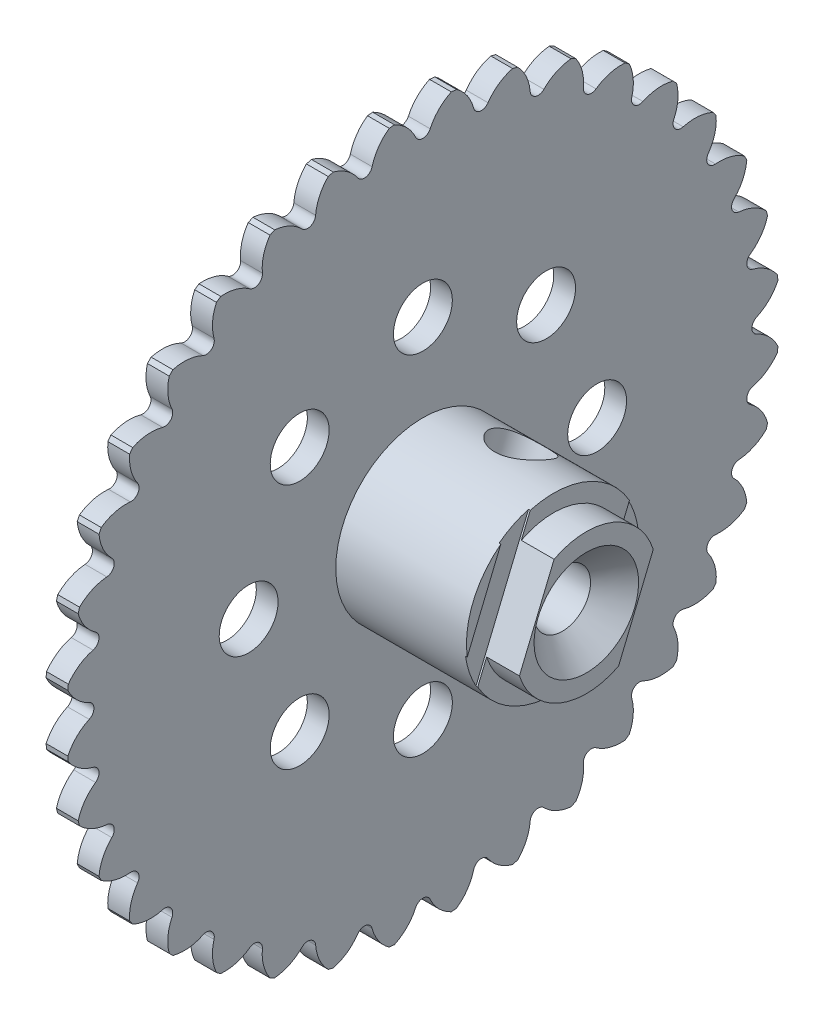
SolidWorks part; units mm, degrees
ref_plane "Front Plane" through (0, 0, 0) normal (0, 0, 1) x (1, 0, 0)
ref_plane "Top Plane" through (0, 0, 0) normal (0, 1, 0) x (1, 0, 0)
ref_plane "Right Plane" through (0, 0, 0) normal (1, 0, 0) x (0, 0, -1)
sketch "Sketch1" plane through (0, 0, 0) normal (1, 0, 0) x (0, 0, -1)
  circle A0 centre (0, 0) radius 25.9588
  dimension "D1" = 51.9176
extrude "Boss-Extrude1" add sketch "Sketch1" along normal blind 1.5875
sketch "Sketch2" plane through (1.5875, 0, 0) normal (1, 0, 0) x (0, 0, -1)
  circle A0 centre (0, 0) radius 12.7 construction
  circle A1 centre (0, 12.7) radius 2.1463
  dimension "D1" = 25.4
  dimension "D2" = 4.2926
extrude "Cut-Extrude1" cut sketch "Sketch2" against normal blind 1.5875
pattern_circular "CirPattern1" count 8 over 360 about axis through (1.5875, 0, 0) along (1, 0, 0) of "Cut-Extrude1"
sketch "Sketch4" plane through (1.5875, 0, 0) normal (1, 0, 0) x (0, 0, -1)
  line L0 (0, 23.9776) -> (0, 25.9588) construction
  line L1 (0, 0.8731) -> (0, -0.8731) construction
  line L2 (0, 0) -> (-2.0726, 25.8759) construction
  line L3 (0, 0) -> (2.4522, 25.8427) construction
  arc A0 (-2.0726, 25.8759) -> (-0.5315, 24.3192) centre (-3.4198, 23.0009) cw
  circle A1 centre (0, 0) radius 25.9588 construction
  arc A2 (-0.5315, 24.3192) -> (0.5315, 24.3192) centre (0, 24.5618) ccw
  arc A3 (0.5315, 24.3192) -> (2.0726, 25.8759) centre (3.4198, 23.0009) cw
  arc A4 (-2.0726, 25.8759) -> (2.4522, 25.8427) centre (0, 0) cw
  circle M13 centre (0, 0) radius 25.9588
  dimension "D1" = 0.5842
  dimension "D2" = 3.175
  dimension "D3" = 1.9812
  dimension "D4" = 10
  dimension "D5" = 0.381
extrude "Cut-Extrude2" cut sketch "Sketch4" against normal blind 1.5875 contours A2 A3 A0 M13 region at (1.5875, 25.2328, 0)
pattern_circular "CirPattern2" count 36 over 360 about axis through (1.5875, 0, 0) along (1, 0, 0) of "Cut-Extrude2"
sketch "Sketch7" plane through (1.5875, 0, 0) normal (1, 0, 0) x (0, 0, -1)
  circle A0 centre (0, 0) radius 6.35
  dimension "D1" = 12.7
extrude "Boss-Extrude3" add sketch "Sketch7" along normal blind 9.525
sketch "Sketch8" plane through (11.1125, 0, 0) normal (1, 0, 0) x (0, 0, -1)
  line L0 (-4.877, -1.5525) -> (-2.3507, 4.5463)
  line L1 (2.3507, -4.5463) -> (4.877, 1.5525)
  line L3 (0, 5.1181) -> (0, -5.1181) construction
  arc A0 (-4.877, -1.5525) -> (2.3507, -4.5463) centre (0, 0) ccw
  arc A1 (4.877, 1.5525) -> (-2.3507, 4.5463) centre (0, 0) ccw
  dimension "D3" = 10.2362
  dimension "D1" = 22.5
  dimension "D2" = 7.8232
extrude "Boss-Extrude4" add sketch "Sketch8" along normal blind 2.3876
sketch "Sketch9" plane through (13.5001, 0, 0) normal (1, 0, 0) x (0, 0, -1)
  circle A0 centre (0, 0) radius 2.0574
  dimension "D1" = 4.1148
extrude "Cut-Extrude3" cut sketch "Sketch9" against normal through all contours A0
sketch "Sketch10" plane through (11.1125, 0, 0) normal (1, 0, 0) x (0, 0, -1)
  line L0 (-5.5281, -3.1245) -> (-1.6996, 6.1183)
  line L1 (-2.3507, 4.5463) -> (-4.877, -1.5525) construction
  line L2 (-6.2923, -0.8542) -> (-3.8453, 5.0534)
  line L3 (-3.9537, -9.545) -> (3.9537, 9.545) construction
  line L4 (3.8453, -5.0534) -> (6.2923, 0.8542)
  line L5 (1.6996, -6.1183) -> (5.5281, 3.1245)
  circle A0 centre (0, 0) radius 6.35 construction
  circle A1 centre (0, 0) radius 6.35 construction
  arc A4 (-1.6996, 6.1183) -> (-3.8453, 5.0534) centre (0, 0) ccw
  arc A5 (-5.5281, -3.1245) -> (-6.2923, -0.8542) centre (0, 0) cw
  arc A6 (1.6996, -6.1183) -> (3.8453, -5.0534) centre (0, 0) ccw
  arc A7 (5.5281, 3.1245) -> (6.2923, 0.8542) centre (0, 0) cw
  point P17 (0, 0)
  dimension "D1" = 1.5748
extrude "Cut-Extrude4" cut sketch "Sketch10" against normal blind 0.127
sketch "Sketch11" plane through (0, 0, 0) normal (0, 0, 1) x (1, 0, 0)
  line L3 (13.5001, -3.81) -> (13.5001, 3.81)
  line L5 (13.5001, 4.5463) -> (13.5001, -1.5525) construction
  line L6 (13.5001, 3.81) -> (9.6901, 0)
  line L7 (9.6901, 0) -> (13.5001, -3.81)
  line L8 (13.5001, 0) -> (9.6901, 0) construction
  point P3 (13.5001, 0)
  dimension "D1" = 90
  dimension "D2" = 7.62
revolve "Cut-Revolve4" cut sketch "Sketch11" angle 360 about L8 region at (12.2301, 1.27, 0)
ref_plane "Plane1" through (0, 0, 0) normal (0, -0.3827, -0.9239) x (-1, 0, 0)
sketch "Sketch12" plane through (0, 0, 0) normal (0, -0.3827, -0.9239) x (-1, 0, 0)
  line L0 (-6.35, -6.35) -> (-6.35, 6.35)
  line L1 (-1.5875, 6.35) -> (-11.1125, 6.35) construction
  line L2 (-8.3344, -6.35) -> (-8.3344, 6.35)
  line L3 (-11.1125, -6.35) -> (-1.5875, -6.35) construction
  line L4 (-8.3344, 6.35) -> (-6.35, 6.35)
  line L5 (-8.3344, -6.35) -> (-6.35, -6.35)
  point P5 (-6.35, 0)
  dimension "D1" = 4.7625
  dimension "D2" = 1.9844
revolve "Cut-Revolve5" cut sketch "Sketch12" angle 360 about L0
